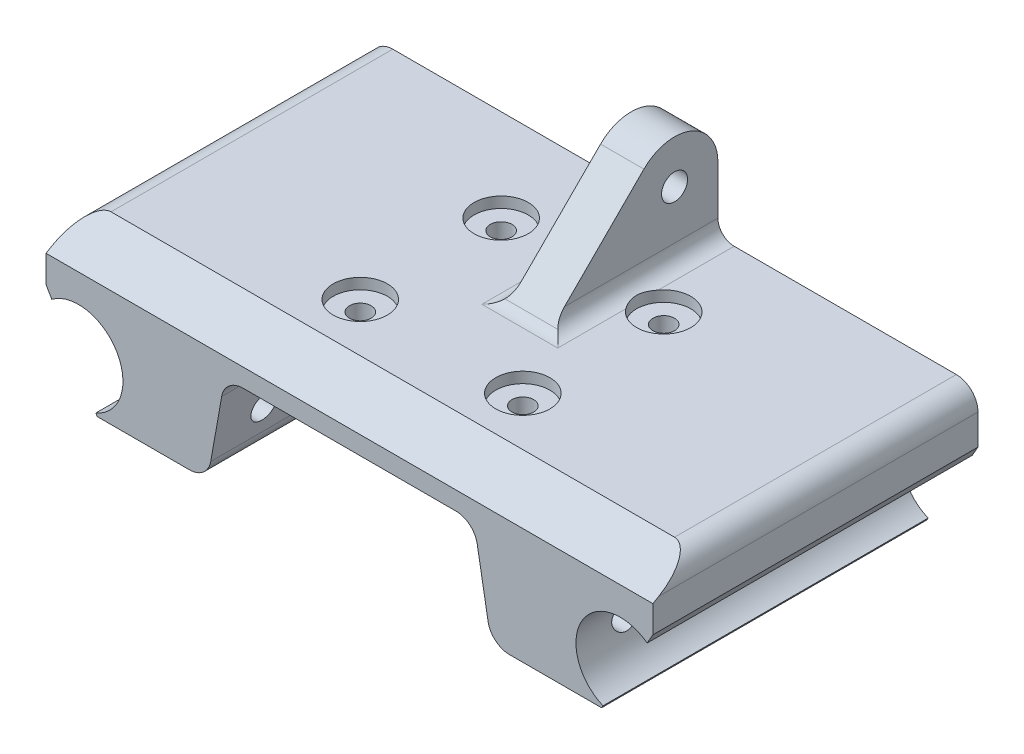
SolidWorks part; units mm, degrees
material "ABS"
ref_plane "Plan de face" through (0, 0, 0) normal (0, 0, 1) x (1, 0, 0)
ref_plane "Plan de dessus" through (0, 0, 0) normal (0, 1, 0) x (1, 0, 0)
ref_plane "Plan de droite" through (0, 0, 0) normal (1, 0, 0) x (0, 0, -1)
sketch "Esquisse1" plane through (0, 0, 0) normal (0, 0, 1) x (1, 0, 0)
  line L0 (0, 0) -> (-28, 0)
  line L1 (-28, 0) -> (-28, -4.8038)
  line L2 (-28, -4.8038) -> (-27.4677, -5.7258)
  line L3 (-23.2679, -13) -> (-23.3983, -12.7742)
  line L4 (-23.2679, -13) -> (-13.0869, -13)
  line L5 (-13.0869, -13) -> (-11.5, -4)
  line L6 (-11.5, -4) -> (0, -4)
  line L7 (0, -4) -> (0, 0)
  arc A0 (-23.3983, -12.7742) -> (-27.4677, -5.7258) centre (-25, -9) ccw
  dimension "D2" = 8.2
  dimension "D4" = 4
  dimension "D8" = 25
  dimension "D1" = 9
  dimension "D3" = 60
  dimension "D5" = 4
  dimension "D6" = 0.5
  dimension "D7" = 11.5
  dimension "D9" = 3
  dimension "D10" = 80
extrude "Boss.-Extru.1" add sketch "Esquisse1" along normal blind 30
sketch "Esquisse3" plane through (0, 0, 0) normal (0, 1, 0) x (1, 0, 0)
  line L0 (0, -30) -> (0, 0) construction
  line L1 (0, 0) -> (-28, 0) construction
  line L2 (0, -30) -> (-28, -30) construction
  circle A0 centre (-7.5, -8.5) radius 1
  circle A1 centre (-7.5, -21.5) radius 1
  dimension "D1" = 2
  dimension "D2" = 7.5
  dimension "D3" = 13
  dimension "D4" = 8.5
  dimension "D5" = 8.5
extrude "Enlèv. mat.-Extru.1" cut sketch "Esquisse3" against normal through all
sketch "Esquisse4" plane through (0, 0, 0) normal (-1, 0, 0) x (0, 0, 1)
  line L4 (30, -13) -> (0, -13) construction
  line L5 (0, -13) -> (0, -4) construction
  circle A0 centre (4.5, -9) radius 1.2
  circle A1 centre (25.5, -9) radius 1.2
  dimension "D1" = 4
  dimension "D2" = 21
  dimension "D3" = 4.5
  dimension "D5" = 2.4
extrude "Enlèv. mat.-Extru.2" cut sketch "Esquisse4" along normal through all
fillet "Congé1" radius 2 3 edges at (-28, 0, 15) (-13.0869, -13, 15) (-11.5, -4, 15)
mirror "Symétrie1" about plane through (0, -4, 30) normal (-1, 0, 0) of bodies 104
sketch "Esquisse2" plane through (0, 0, 0) normal (1, 0, 0) x (0, 0, -1)
  line L1 (0, 0) -> (-15.6569, 0)
  line L2 (0, 0) -> (0, 6)
  line L4 (-15.6569, 0) -> (-6.8284, 8.8284)
  arc A0 (0, 6) -> (-6.8284, 8.8284) centre (-4, 6) ccw
  circle A1 centre (-4, 6) radius 1.2
  dimension "D1" = 2.4
  dimension "D2" = 4
  dimension "D3" = 6
  dimension "D4" = 45
extrude "Boss.-Extru.2" add sketch "Esquisse2" along normal blind 4
fillet "Congé2" radius 1.5 3 edges at (0, 0, 7.8284) (2, 0, 15.6569) (4, 0, 7.8284)
sketch "Esquisse5" plane through (0, 0, 0) normal (0, 1, 0) x (1, 0, 0)
  circle A0 centre (-7.5, -8.5) radius 2.5
  circle A1 centre (-7.5, -21.5) radius 2.5
  circle A2 centre (7.5, -8.5) radius 2.5
  circle A3 centre (7.5, -21.5) radius 2.5
  circle A4 centre (-7.5, -21.5) radius 1 construction
  circle A5 centre (7.5, -8.5) radius 1 construction
  circle A6 centre (7.5, -21.5) radius 1 construction
  dimension "D1" = 5
extrude "Enlèv. mat.-Extru.3" cut sketch "Esquisse5" against normal blind 1 and the other way through all
ref_axis "Axe1" through (4, 6, 4) along (-1, 0, 0)
ref_plane "Plan1" through (0, 6, 0) normal (0, 1, 0) x (1, 0, 0)
chamfer "Chanfrein1" distance 4 angle 30 1 edges at (0, 0, 30) tangent propagation no first distance on face at (2.35, 0, 10.9556)
